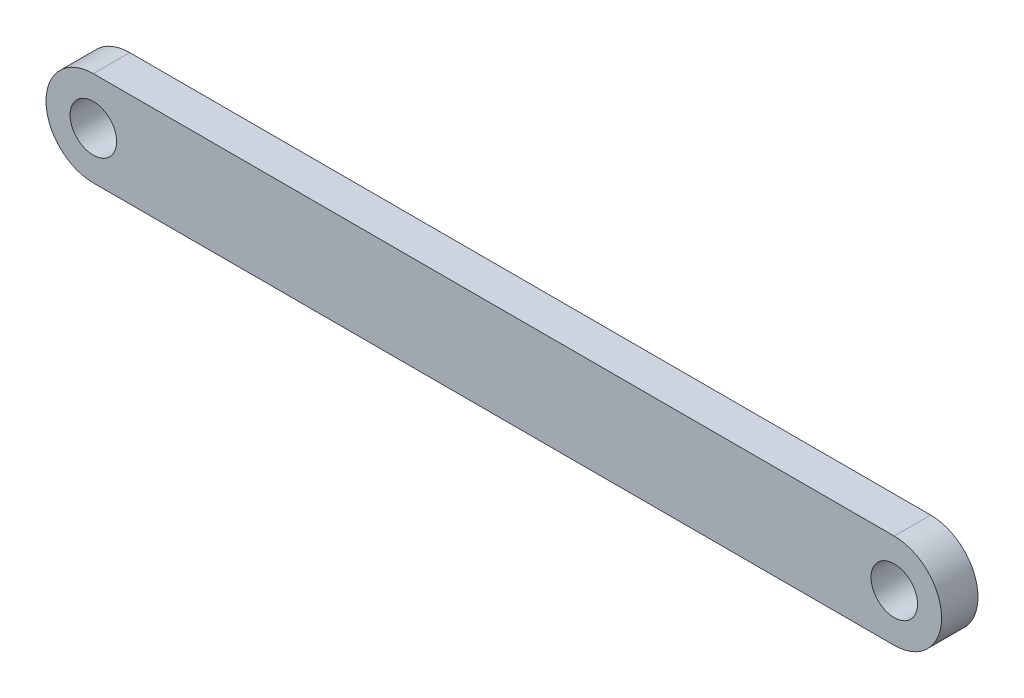
SolidWorks part; units mm, degrees
ref_plane "Front Plane" through (0, 0, 0) normal (0, 0, 1) x (1, 0, 0)
ref_plane "Top Plane" through (0, 0, 0) normal (0, 1, 0) x (1, 0, 0)
ref_plane "Right Plane" through (0, 0, 0) normal (1, 0, 0) x (0, 0, -1)
sketch "Sketch1" plane through (0, 0, 0) normal (0, 0, 1) x (1, 0, 0)
  line L0 (-55, 0) -> (0, 0) construction
  line L1 (-55, 3.25) -> (0, 3.25)
  line L2 (-55, -3.25) -> (0, -3.25)
  arc A0 (-55, 3.25) -> (-55, -3.25) centre (-55, 0) ccw
  arc A1 (0, -3.25) -> (0, 3.25) centre (0, 0) ccw
  circle A2 centre (-55, 0) radius 1.6
  circle A3 centre (0, 0) radius 1.6
  point P2 (-27.5, 0)
  point P11 (0, 0)
  dimension "D1" = 3.25
  dimension "D3" = 3.2
  dimension "D2" = 55
extrude "Boss-Extrude1" add sketch "Sketch1" along normal blind 2.5
